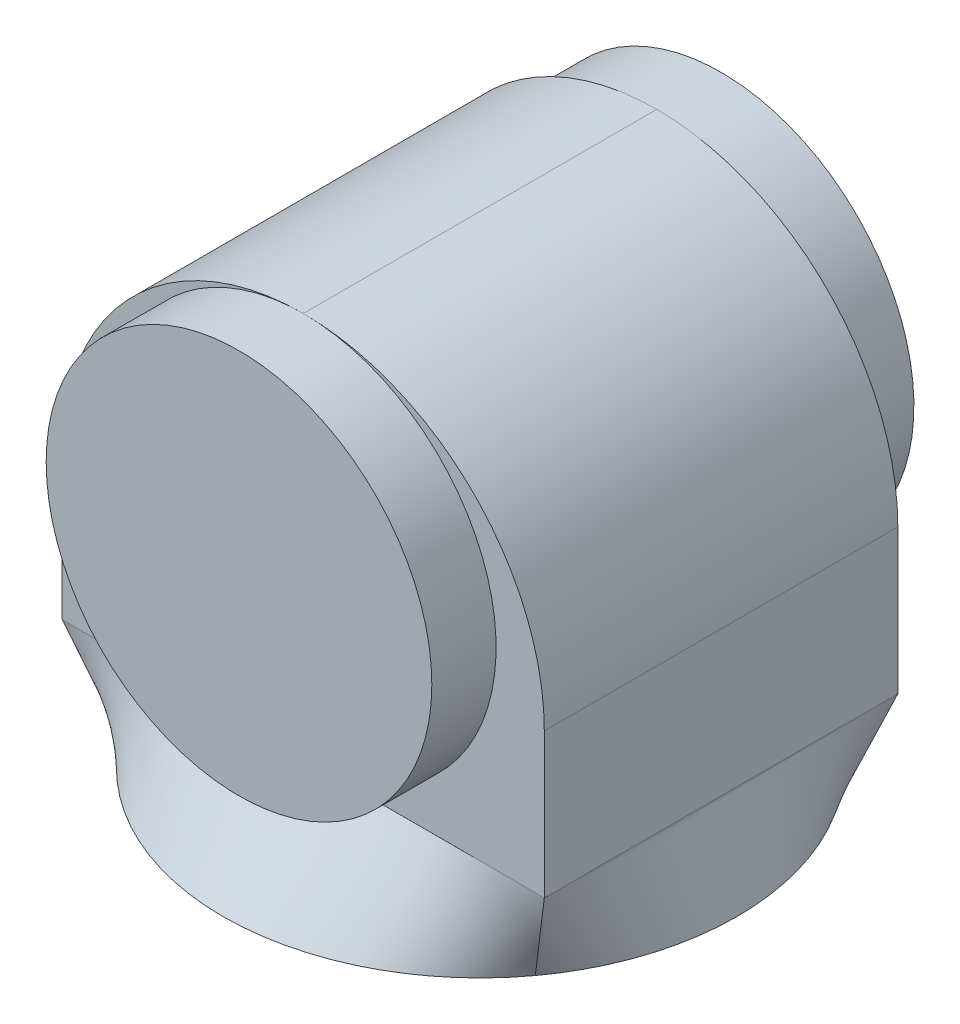
SolidWorks part; units mm, degrees
material "6061-T6 (SS)"
ref_plane "Ebene vorne" through (0, 0, 0) normal (0, 0, 1) x (1, 0, 0)
ref_plane "Ebene oben" through (0, 0, 0) normal (0, 1, 0) x (1, 0, 0)
ref_plane "Ebene rechts" through (0, 0, 0) normal (1, 0, 0) x (0, 0, -1)
sketch "Skizze1" plane through (0, 0, 0) normal (0, 1, 0) x (1, 0, 0)
  circle A0 centre (0, 0) radius 80
  dimension "D1" = 160
ref_plane "Ebene1" through (0, 30, 0) normal (0, 1, 0) x (1, 0, 0)
sketch "Skizze2" plane through (0, 30, 0) normal (0, 1, 0) x (1, 0, 0)
  line L1 (-75, -55) -> (75, -55)
  line L2 (-75, -55) -> (-75, 55)
  line L3 (-75, 55) -> (75, 55)
  line L4 (75, -55) -> (75, 55)
  line L5 (-75, -55) -> (75, 55) construction
  line L6 (-75, 55) -> (75, -55) construction
  point P0 (0, 0)
  dimension "D1" = 150
  dimension "D2" = 110
loft "Ausformung1" add profiles "Skizze1", "Skizze2" connector at (-10.824, 0, 79.2644) connector at (-75, 30, 55)
sketch "Skizze4" plane through (0, 30, 0) normal (0, 1, 0) x (1, 0, 0)
  line L4 (75, -55) -> (75, 55)
  line L5 (75, 55) -> (-75, 55)
  line L6 (-75, 55) -> (-75, -55)
  line L7 (-75, -55) -> (75, -55)
  line L8 (75, -55) -> (75, 55)
  line L9 (75, 55) -> (-75, 55)
  line L10 (-75, 55) -> (-75, -55)
  line L11 (-75, -55) -> (75, -55)
  dimension "D1" = 0
extrude "Aufsatz-Linear austragen1" add sketch "Skizze4" along normal blind 120
sketch "Skizze5" plane through (-20, 0, 55) normal (0, 0, -1) x (-1, 0, 0)
  line L0 (-20, 150) -> (-20, 30) construction
  line L3 (55, 150) -> (-95, 150) construction
  line L4 (55, 30) -> (-95, 30) construction
  circle A0 centre (-20, 90) radius 60
  dimension "D1" = 120
extrude "Aufsatz-Linear austragen2" add sketch "Skizze5" against normal blind 20
mirror "Spiegeln1" about plane through (0, 0, 0) normal (0, 0, 1) of "Aufsatz-Linear austragen2"
fillet "Verrundung1" radius 75 2 edges at (75, 150, 0) (-75, 150, 0)
